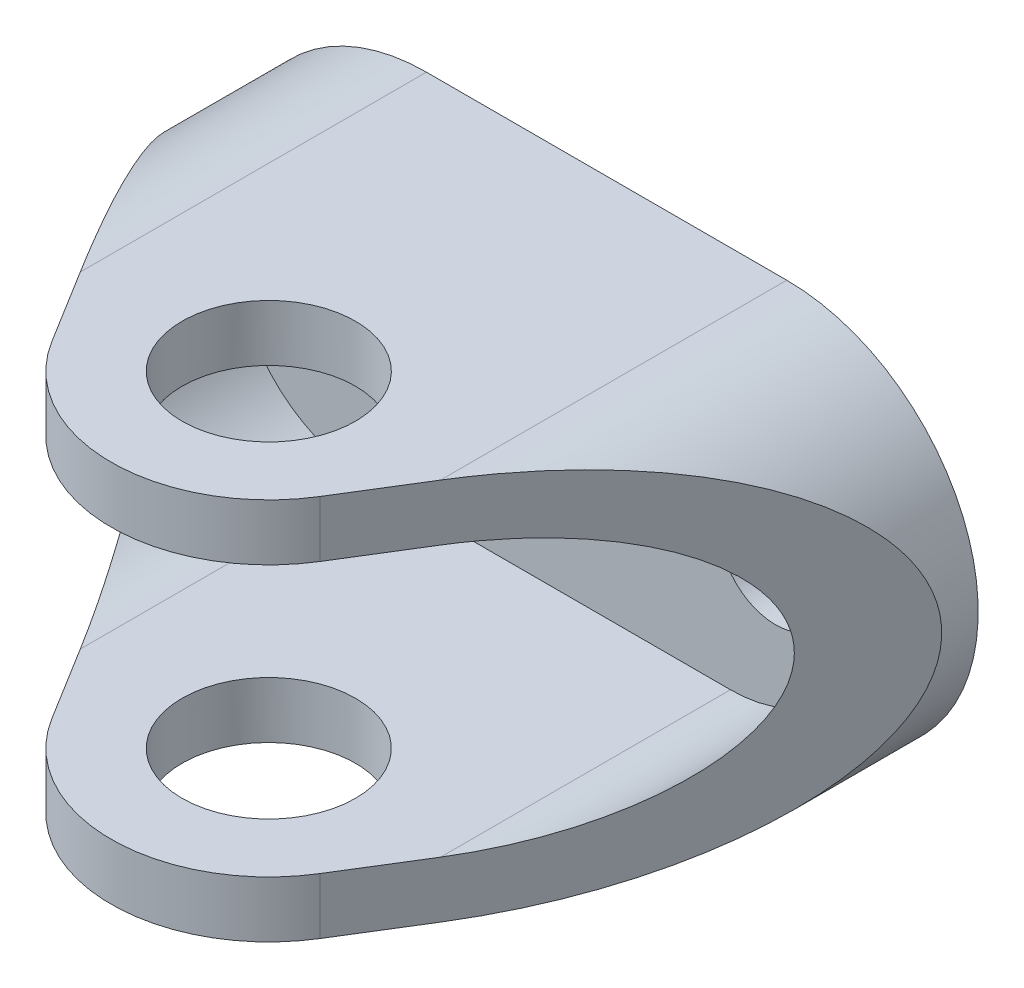
SolidWorks part; units mm, degrees
material "6061 Alloy"
ref_plane "Front Plane" through (0, 0, 0) normal (0, 0, 1) x (1, 0, 0)
ref_plane "Top Plane" through (0, 0, 0) normal (0, 1, 0) x (1, 0, 0)
ref_plane "Right Plane" through (0, 0, 0) normal (1, 0, 0) x (0, 0, -1)
sketch "Sketch1" plane through (0, 0, 0) normal (0, 1, 0) x (1, 0, 0)
  line L0 (-22.225, -15.875) -> (22.225, -15.875)
  line L1 (-22.225, -15.875) -> (-22.225, 15.875)
  line L2 (22.225, -15.875) -> (22.225, 15.875)
  line L3 (-22.225, 15.875) -> (22.225, 15.875)
  line L4 (-22.225, -15.875) -> (22.225, 15.875) construction
  line L5 (22.225, -15.875) -> (-22.225, 15.875) construction
  point P1 (0, 0)
  dimension "D1" = 31.75
  dimension "D2" = 44.45
extrude "Billet" add sketch "Sketch1" along normal blind 21.59
sketch "Sketch2" plane through (0, 21.59, 0) normal (0, 1, 0) x (1, 0, 0)
  line L1 (-7.5622, -7.8489) -> (-22.225, 15.875)
  line L4 (-22.225, 15.875) -> (22.225, 15.875) construction
  line L5 (0, -14.605) -> (0, -11.9174) construction
  line L6 (-22.225, 15.875) -> (-22.225, -15.875)
  line L7 (-22.225, -15.875) -> (22.225, -15.875)
  line L8 (22.225, -15.875) -> (22.225, 15.875)
  line L9 (7.5622, -7.8489) -> (22.225, 15.875)
  line L10 (22.225, 15.875) -> (-22.225, 15.875) construction
  arc A0 (7.5622, -7.8489) -> (-7.5622, -7.8489) centre (0, -3.175) cw
  circle A1 centre (0, -3.175) radius 4.8895
  line M1 (-22.225, 15.875) -> (-22.225, -15.875)
  line M2 (-22.225, -15.875) -> (22.225, -15.875)
  line M3 (22.225, -15.875) -> (22.225, 15.875)
  dimension "D1" = 8.89
  dimension "D3" = 9.779
  dimension "D4" = 19.05
extrude "Mill Cut 1" cut sketch "Sketch2" against normal through all contours L9 A0 L1 M1 M2 M3 | A1 region at (0, 21.59, 12.6112) region at (0, 21.59, 3.175)
ref_plane "Plane2" through (0, 21.59, 12.065) normal (0, 0, 1) x (1, 0, 0)
sketch "Sketch6" plane through (0, 21.59, 12.065) normal (0, 0, 1) x (1, 0, 0)
  line L0 (7.5622, 0) -> (-7.5622, 0) construction
  line L1 (-10.16, -3.175) -> (10.16, -3.175)
  line L3 (-10.16, -18.415) -> (10.16, -18.415)
  line L5 (0, -3.175) -> (0, 0) construction
  line L6 (0, -18.415) -> (0, -21.59) construction
  arc A0 (-10.16, -3.175) -> (-10.16, -18.415) centre (-10.16, -10.795) ccw
  arc A1 (10.16, -3.175) -> (10.16, -18.415) centre (10.16, -10.795) cw
  point P6 (0, 0)
  point P7 (0, -3.175)
  dimension "D1" = 3.175
  dimension "D2" = 10.16
extrude "Cut-Extrude1" cut sketch "Sketch6" against normal offset from surface (24.765 mm away) 3.175 contours L1 L3 region at (0, 10.795, 12.065) up to face at (0, 10.795, -15.875)
sketch "Sketch8" plane through (0, 21.59, 12.065) normal (0, 0, 1) x (1, 0, 0)
  line L7 (-7.5622, 0) -> (-22.225, 0) construction
  line L8 (-10.16, -21.59) -> (-60.96, -21.59)
  line L9 (-60.96, -21.59) -> (-60.96, 0)
  line L10 (-60.96, 0) -> (-10.16, 0)
  line L11 (-7.5622, -21.59) -> (-22.225, -21.59) construction
  arc A4 (-10.16, 0) -> (-10.16, -21.59) centre (-10.16, -10.795) ccw
  arc A8 (-10.16, -3.175) -> (-10.16, -18.415) centre (-10.16, -10.795) ccw construction
  dimension "D1" = 50.8
extrude "Cut-Extrude2" cut sketch "Sketch8" against normal through all
mirror "Mirror1" about plane through (0, 0, 0) normal (1, 0, 0) of "Cut-Extrude2"
sketch "Sketch9" plane through (0, 0, -12.7) normal (0, 0, 1) x (1, 0, 0)
  line L0 (0, 21.59) -> (0, 0) construction
  line L1 (7.5622, 21.59) -> (-7.5622, 21.59) construction
  line L2 (0, 10.795) -> (12.7, 10.795) construction
  circle A0 centre (12.7, 10.795) radius 3.175
  circle A1 centre (-12.7, 10.795) radius 3.175
  dimension "D1" = 6.35
  dimension "D2" = 12.7
extrude "Holes" cut sketch "Sketch9" against normal through all
ref_axis "Axis1" [suppressed] through (0, 18.415, 0.635) along (0, 1, 0)
ref_plane "Plane1" [suppressed] through (0.2984, 0, 0.4261) normal (-0.5736, 0, -0.8192) x (0, 1, 0)
sketch "Sketch5" [suppressed] plane through (0, 21.59, 0) normal (0, 1, 0) x (1, 0, 0)
  circle A0 centre (0, -0.635) radius 4.8895
extrude "Mock Bolt" [suppressed] add sketch "Sketch5" against normal through all
